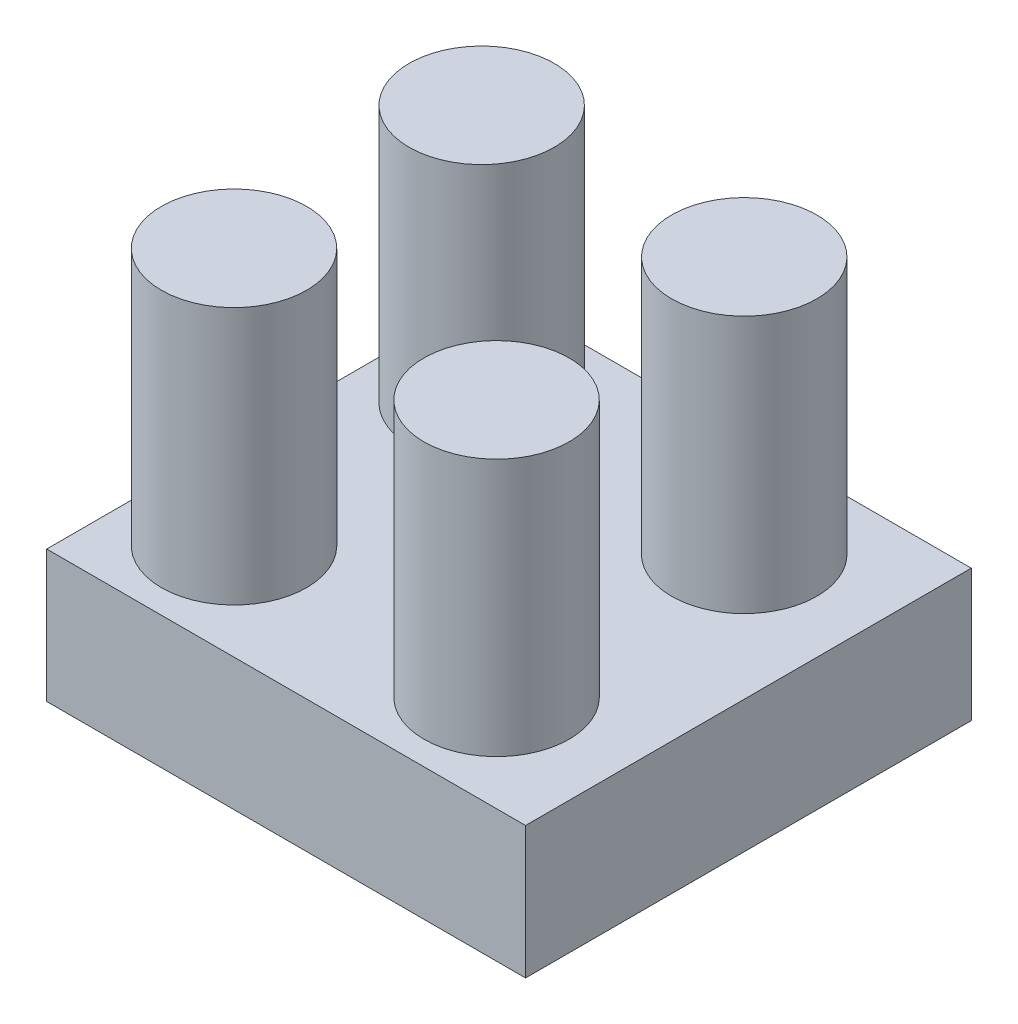
SolidWorks part; units mm, degrees
ref_plane "Front Plane" through (0, 0, 0) normal (0, 0, 1) x (1, 0, 0)
ref_plane "Top Plane" through (0, 0, 0) normal (0, 1, 0) x (1, 0, 0)
ref_plane "Right Plane" through (0, 0, 0) normal (1, 0, 0) x (0, 0, -1)
sketch "Sketch1" plane through (0, 0, 0) normal (0, 1, 0) x (1, 0, 0)
  line L0 (7.25, 0) -> (-7.25, 0) construction
  line L1 (-7.25, 8.1) -> (7.25, 8.1)
  line L2 (-7.25, 8.1) -> (-7.25, -8.1)
  line L3 (-7.25, -8.1) -> (7.25, -8.1)
  line L4 (7.25, 8.1) -> (7.25, -8.1)
  line L5 (-7.25, 8.1) -> (7.25, -8.1) construction
  line L6 (-7.25, -8.1) -> (7.25, 8.1) construction
  line L7 (7.25, -3.75) -> (3.45, -3.75) construction
  line L8 (3.45, -3.75) -> (3.45, -8.1) construction
  line L9 (3.45, -3.75) -> (-4.5, -3.75) construction
  circle A0 centre (3.45, -3.75) radius 2.2
  circle A1 centre (-4.5, -3.75) radius 2.2
  circle A2 centre (-4.5, 3.75) radius 2.2
  circle A3 centre (3.45, 3.75) radius 2.2
  point P0 (0, 0)
  point P18 (0, 0)
  point P19 (0, 0)
  point P20 (-4.5, 3.75)
  dimension "D5" = 4.4
  dimension "D7" = 4.4
  dimension "D1" = 14.5
  dimension "D2" = 16.2
  dimension "D3" = 4.35
  dimension "D4" = 3.8
  dimension "D6" = 7.95
extrude "Boss-Extrude2" add sketch "Sketch1" along normal blind 4
sketch "Sketch2" plane through (0, 4, 0) normal (0, 1, 0) x (1, 0, 0)
  circle A0 centre (3.45, 3.75) radius 2.2
  circle A1 centre (-4.5, 3.75) radius 2.2
  circle A2 centre (3.45, -3.75) radius 2.2
  circle A3 centre (-4.5, -3.75) radius 2.2
  point P12 (0, 0)
extrude "Boss-Extrude3" add sketch "Sketch2" along normal blind 7.8 and the other way up to surface (4 mm away) separate body other way up to face at (0, 0, 0)
sketch "Sketch4" plane through (0, 4, 0) normal (0, 1, 0) x (1, 0, 0)
  line L0 (7.25, -8.1) -> (7.25, 8.1) construction
  line L1 (-7.25, 8.1) -> (7.25, 8.1)
  line L2 (-7.25, 8.1) -> (-7.25, 6.8251)
  line L3 (-7.25, 6.8251) -> (7.25, 6.8251)
  line L4 (7.25, 8.1) -> (7.25, 6.8251)
  line L6 (-7.25, -8.1) -> (7.25, -8.1)
  line L7 (-7.25, -8.1) -> (-7.25, -6.6715)
  line L8 (-7.25, -6.6715) -> (7.25, -6.6715)
  line L9 (7.25, -8.1) -> (7.25, -6.6715)
extrude "Cut-Extrude1" cut sketch "Sketch4" against normal blind 9.8
